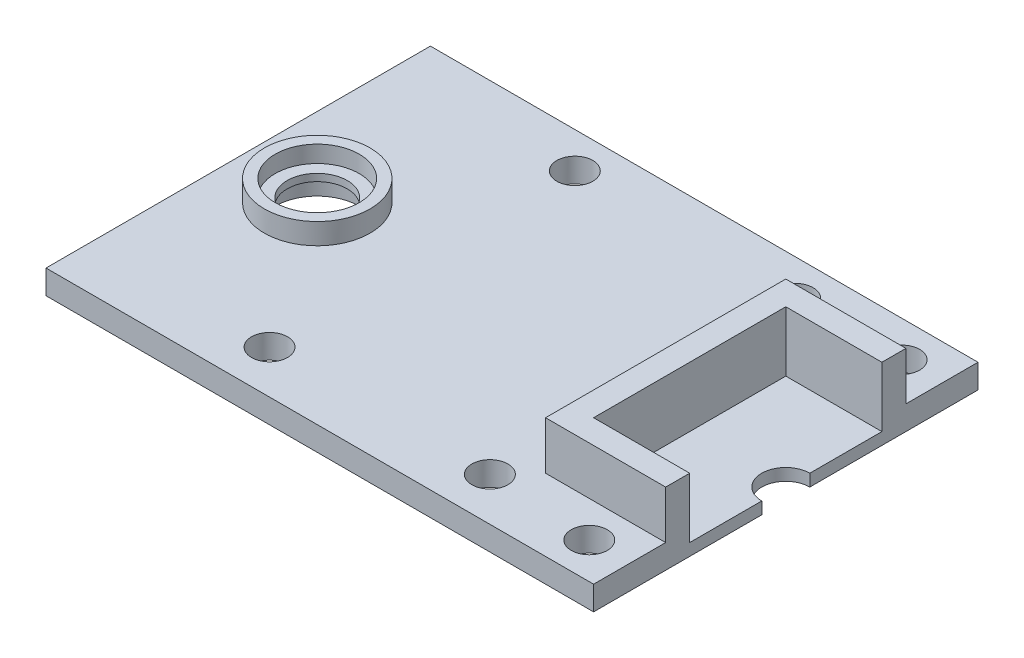
SolidWorks part; units mm, degrees
ref_plane "Front Plane" through (0, 0, 0) normal (0, 0, 1) x (1, 0, 0)
ref_plane "Top Plane" through (0, 0, 0) normal (0, 1, 0) x (1, 0, 0)
ref_plane "Right Plane" through (0, 0, 0) normal (1, 0, 0) x (0, 0, -1)
sketch "Sketch1" plane through (0, 0, 0) normal (0, 1, 0) x (1, 0, 0)
  line L1 (-279.4, -50.8) -> (0, -50.8)
  line L2 (-279.4, -50.8) -> (-279.4, 50.8)
  line L3 (-279.4, 50.8) -> (0, 50.8)
  line L4 (0, -50.8) -> (0, 50.8)
  point P0 (0, 0)
  dimension "D1" = 279.4
  dimension "D2" = 101.6
extrude "Boss-Extrude1" add sketch "Sketch1" along normal blind 6.35
sketch "Sketch2" plane through (0, 6.35, 0) normal (0, 1, 0) x (1, 0, 0)
  line L0 (-279.4, 50.8) -> (-279.4, -50.8) construction
  line L2 (0, 50.8) -> (-279.4, 50.8) construction
  circle A0 centre (-258.5106, 0) radius 13.97
  dimension "D1" = 50.8
  dimension "D2" = 27.94
  dimension "D3" = 20.8894
extrude "Boss-Extrude3" add sketch "Sketch2" along normal blind 5.5562
sketch "Sketch9" plane through (0, 11.9062, 0) normal (0, 1, 0) x (1, 0, 0)
  circle A0 centre (-258.5106, 0) radius 11.1125
extrude "Cut-Extrude4" cut sketch "Sketch9" against normal blind 4.445
sketch "Sketch10" plane through (0, 0, 0) normal (0, -1, 0) x (-1, 0, 0)
  circle A0 centre (258.5106, 0) radius 11.1125
extrude "Cut-Extrude5" cut sketch "Sketch10" against normal blind 5.5562
sketch "Sketch11" plane through (0, 7.4613, 0) normal (0, 1, 0) x (1, 0, 0)
  circle A0 centre (-258.5106, 0) radius 7.9375
extrude "Cut-Extrude6" cut sketch "Sketch11" against normal through all
sketch "Sketch12" plane through (0, 6.35, 0) normal (0, 1, 0) x (1, 0, 0)
  line L0 (0, 50.8) -> (-279.4, 50.8) construction
  line L1 (-279.4, 50.8) -> (-279.4, -50.8) construction
  circle A0 centre (-134.6662, 0) radius 6.35
  dimension "D1" = 12.7
  dimension "D2" = 50.8
  dimension "D3" = 144.7338
extrude "Cut-Extrude7" cut sketch "Sketch12" against normal through all
sketch "Sketch22" plane through (0, 6.35, 0) normal (0, 1, 0) x (1, 0, 0)
  line L1 (-102.9162, -31.75) -> (-166.4162, -31.75)
  line L2 (-102.9162, -31.75) -> (-102.9162, 31.75)
  line L3 (-102.9162, 31.75) -> (-166.4162, 31.75)
  line L4 (-166.4162, -31.75) -> (-166.4162, 31.75)
  line L5 (-102.9162, -31.75) -> (-166.4162, 31.75) construction
  line L6 (-102.9162, 31.75) -> (-166.4162, -31.75) construction
  circle A0 centre (-134.6662, 0) radius 6.35 construction
  point P0 (-134.6662, 0)
extrude "Boss-Extrude7" add sketch "Sketch22" along normal blind 12.7
sketch "Sketch25" plane through (0, 19.05, 0) normal (0, 1, 0) x (1, 0, 0)
  line L1 (-109.2662, -25.4) -> (-160.0662, -25.4)
  line L2 (-109.2662, -25.4) -> (-109.2662, 25.4)
  line L3 (-109.2662, 25.4) -> (-160.0662, 25.4)
  line L4 (-160.0662, -25.4) -> (-160.0662, 25.4)
  line L5 (-109.2662, -25.4) -> (-160.0662, 25.4) construction
  line L6 (-109.2662, 25.4) -> (-160.0662, -25.4) construction
  circle A0 centre (-134.6662, 0) radius 6.35 construction
  point P0 (-134.6662, 0)
  dimension "D1" = 50.8
  dimension "D2" = 50.8
extrude "Cut-Extrude11" cut sketch "Sketch25" against normal blind 15.875
sketch "Sketch32" plane through (0, 6.35, 0) normal (0, 1, 0) x (1, 0, 0)
  line L3 (-279.4, -50.8) -> (0, -50.8) construction
  line L5 (0, 50.8) -> (-279.4, 50.8) construction
  circle A0 centre (-67.442, -40.64) radius 4.7625
  circle A1 centre (-81.412, -40.64) radius 4.7625
  circle A2 centre (-67.442, 40.64) radius 4.7625
  circle A3 centre (-81.412, 40.64) radius 4.7625
  dimension "D1" = 10.16
  dimension "D2" = 10.16
  dimension "D3" = 10.16
  dimension "D4" = 10.16
  dimension "D5" = 13.97
  dimension "D6" = 13.97
  dimension "D7" = 81.28
extrude "Cut-Extrude12" cut sketch "Sketch32" against normal blind 6.35
sketch "Sketch38" plane through (0, 6.35, 0) normal (0, 1, 0) x (1, 0, 0)
  line L0 (0, -50.8) -> (0, 50.8) construction
  line L1 (0, -34.0128) -> (-46.99, -34.0128)
  line L2 (0, -34.0128) -> (0, -15.5426)
  line L3 (0, -15.5426) -> (-46.99, -15.5426)
  line L4 (-46.99, -34.0128) -> (-46.99, -15.5426)
  line L6 (-279.4, -50.8) -> (0, -50.8) construction
  dimension "D1" = 35.2574
  dimension "D2" = 18.4703
  dimension "D3" = 46.99
extrude "Cut-Extrude13" cut sketch "Sketch38" against normal blind 6.35
sketch "Sketch60" plane through (0, 6.35, 0) normal (0, 1, 0) x (1, 0, 0)
  line L1 (-279.4, 50.8) -> (-279.4, -50.8) construction
  line L2 (0, 50.8) -> (-279.4, 50.8) construction
  circle A0 centre (-231.7492, 41.3241) radius 4.7625
  circle A1 centre (-231.7492, -39.3693) radius 4.7625
  circle A2 centre (-173.5092, -39.3693) radius 4.7625
  circle A3 centre (-173.5092, 41.3241) radius 4.7625
  dimension "D1" = 47.6508
  dimension "D5" = 9.525
  dimension "D6" = 9.525
  dimension "D7" = 9.525
  dimension "D8" = 9.525
  dimension "D2" = 58.24
  dimension "D3" = 80.6935
  dimension "D4" = 9.4759
  dimension "D9" = 105.8908
extrude "Cut-Extrude23" cut sketch "Sketch60" against normal up to surface (6.35 mm away) up to face at (-81.5975, 0, 12.3889)
sketch "Sketch61" plane through (0, 6.35, 0) normal (0, 1, 0) x (1, 0, 0)
  line L0 (-134.6662, 0) -> (-134.6662, 50.8)
  line L1 (0, 50.8) -> (-279.4, 50.8) construction
  line L2 (-134.6662, 0) -> (-134.6662, -50.8)
  line L3 (-279.4, -50.8) -> (0, -50.8) construction
extrude "Cut-Extrude24" cut sketch "Sketch61" against normal through all and the other way through all
sketch "Sketch62" plane through (0, 6.35, 0) normal (0, 1, 0) x (1, 0, 0)
  line L0 (-134.6662, 50.8) -> (-134.6662, 31.75) construction
  line L1 (-134.6662, 50.8) -> (-279.4, 50.8) construction
  circle A0 centre (-145.3342, 41.275) radius 4.7625
  dimension "D1" = 10.668
  dimension "D3" = 9.525
  dimension "D2" = 9.525
extrude "Cut-Extrude25" cut sketch "Sketch62" against normal through all
mirror "Mirror1" about plane through (0, 0, 0) normal (0, 0, 1) of "Cut-Extrude25"
